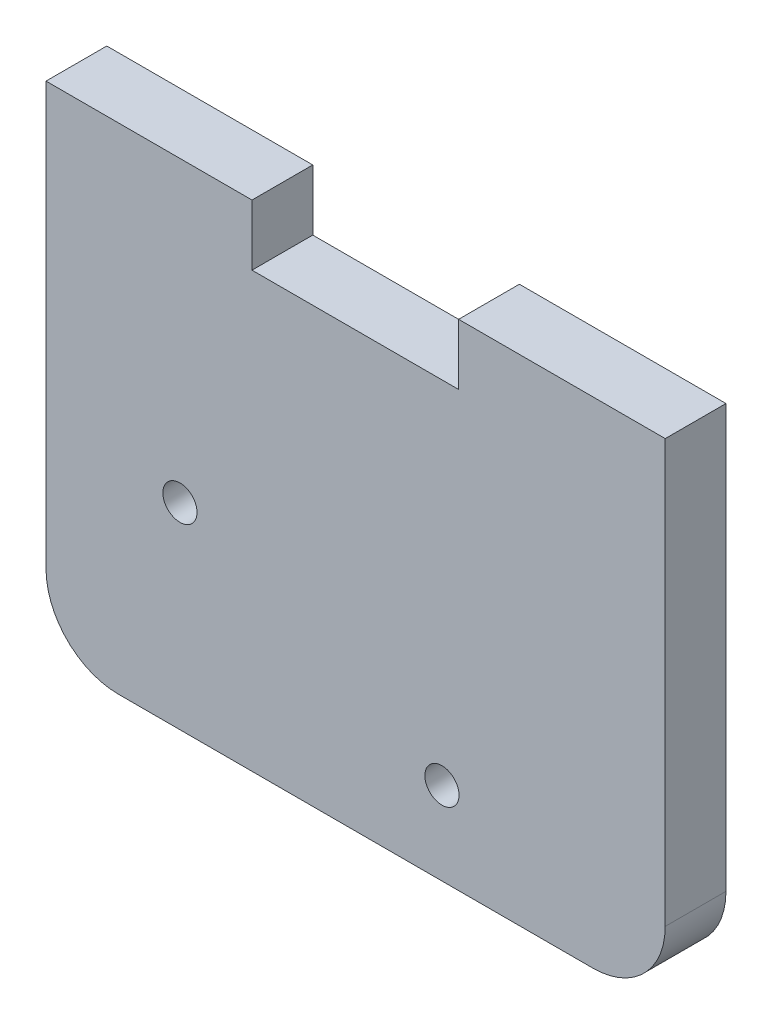
SolidWorks part; units mm, degrees
material "Teak"
ref_plane "Front Plane" through (0, 0, 0) normal (0, 0, 1) x (1, 0, 0)
ref_plane "Top Plane" through (0, 0, 0) normal (0, 1, 0) x (1, 0, 0)
ref_plane "Right Plane" through (0, 0, 0) normal (1, 0, 0) x (0, 0, -1)
sketch "Sketch1" plane through (0, 0, 0) normal (0, 0, 1) x (1, 0, 0)
  line L1 (-30.5325, 25.3111) -> (23.8235, 25.3111)
  line L2 (-30.5325, 25.3111) -> (-30.5325, -18.1229)
  line L3 (-30.5325, -18.1229) -> (23.8235, -18.1229)
  line L4 (23.8235, 25.3111) -> (23.8235, -18.1229)
  dimension "D1" = 43.434
  dimension "D2" = 54.356
extrude "Boss-Extrude1" add sketch "Sketch1" along normal blind 5.334 contours L1 L4 L3 L2
sketch "Sketch2" plane through (0, 0, 5.334) normal (0, 0, 1) x (1, 0, 0)
  line L0 (-30.5325, 25.3111) -> (23.8235, 25.3111) construction
  line L1 (-12.4506, 25.3111) -> (5.6865, 25.3111)
  line L2 (-12.4506, 25.3111) -> (-12.4506, 19.9771)
  line L3 (-12.4506, 19.9771) -> (5.6865, 19.9771)
  line L4 (5.6865, 25.3111) -> (5.6865, 19.9771)
  line L5 (-12.4506, 19.9771) -> (-30.5325, 19.9771) construction
  line L6 (-30.5325, 25.3111) -> (-30.5325, -18.1229) construction
  line L7 (5.6865, 19.9771) -> (23.8235, 19.9771) construction
  line L8 (23.8235, 25.3111) -> (23.8235, -18.1229) construction
  dimension "D1" = 5.334
extrude "Cut-Extrude1" cut sketch "Sketch2" against normal through all
fillet "Fillet1" radius 6.35 2 edges at (-30.5325, -18.1229, 2.667) (23.8235, -18.1229, 2.667)
sketch "Sketch3" plane through (0, 0, 5.334) normal (0, 0, 1) x (1, 0, 0)
  line L8 (-30.5325, 25.3111) -> (-30.5325, -11.7729)
  line L9 (-24.1825, -18.1229) -> (17.4735, -18.1229)
  line L10 (23.8235, -11.7729) -> (23.8235, 25.3111)
  line L11 (23.8235, 25.3111) -> (5.6865, 25.3111)
  line L12 (5.6865, 25.3111) -> (5.6865, 19.9771)
  line L13 (5.6865, 19.9771) -> (-12.4506, 19.9771)
  line L14 (-12.4506, 19.9771) -> (-12.4506, 25.3111)
  line L15 (-12.4506, 25.3111) -> (-30.5325, 25.3111)
  line L16 (-30.5325, 25.3111) -> (-30.5325, -11.7729)
  line L17 (-24.1825, -18.1229) -> (17.4735, -18.1229)
  line L18 (23.8235, -11.7729) -> (23.8235, 25.3111)
  line L19 (23.8235, 25.3111) -> (5.6865, 25.3111)
  line L20 (5.6865, 25.3111) -> (5.6865, 19.9771)
  line L21 (5.6865, 19.9771) -> (-12.4506, 19.9771)
  line L22 (-12.4506, 19.9771) -> (-12.4506, 25.3111)
  line L23 (-12.4506, 25.3111) -> (-30.5325, 25.3111)
  circle A0 centre (-18.7754, -0.8561) radius 1.5 construction
  circle A1 centre (4.2246, -10.8561) radius 1.5 construction
  arc A2 (-30.5325, -11.7729) -> (-24.1825, -18.1229) centre (-24.1825, -11.7729) ccw
  arc A3 (17.4735, -18.1229) -> (23.8235, -11.7729) centre (17.4735, -11.7729) ccw
  arc A4 (-30.5325, -11.7729) -> (-24.1825, -18.1229) centre (-24.1825, -11.7729) ccw
  arc A5 (17.4735, -18.1229) -> (23.8235, -11.7729) centre (17.4735, -11.7729) ccw
  circle A6 centre (-18.7754, -0.8561) radius 1.5
  circle A7 centre (4.2246, -10.8561) radius 1.5
  dimension "D1" = 0
extrude "Cut-Extrude3" cut sketch "Sketch3" against normal through all contours A6 | A7
equation "\"MDF\"= .21in"
equation "\"Foamcore\"= .13in"
equation "\"Gmaterial\"= \"MDF\""
equation "\"D1@Sketch1\"=\"MDF\"+1.5"
equation "\"D1@Boss-Extrude1\"=\"MDF\""
equation "\"D1@Sketch2\"=\"MDF\""
